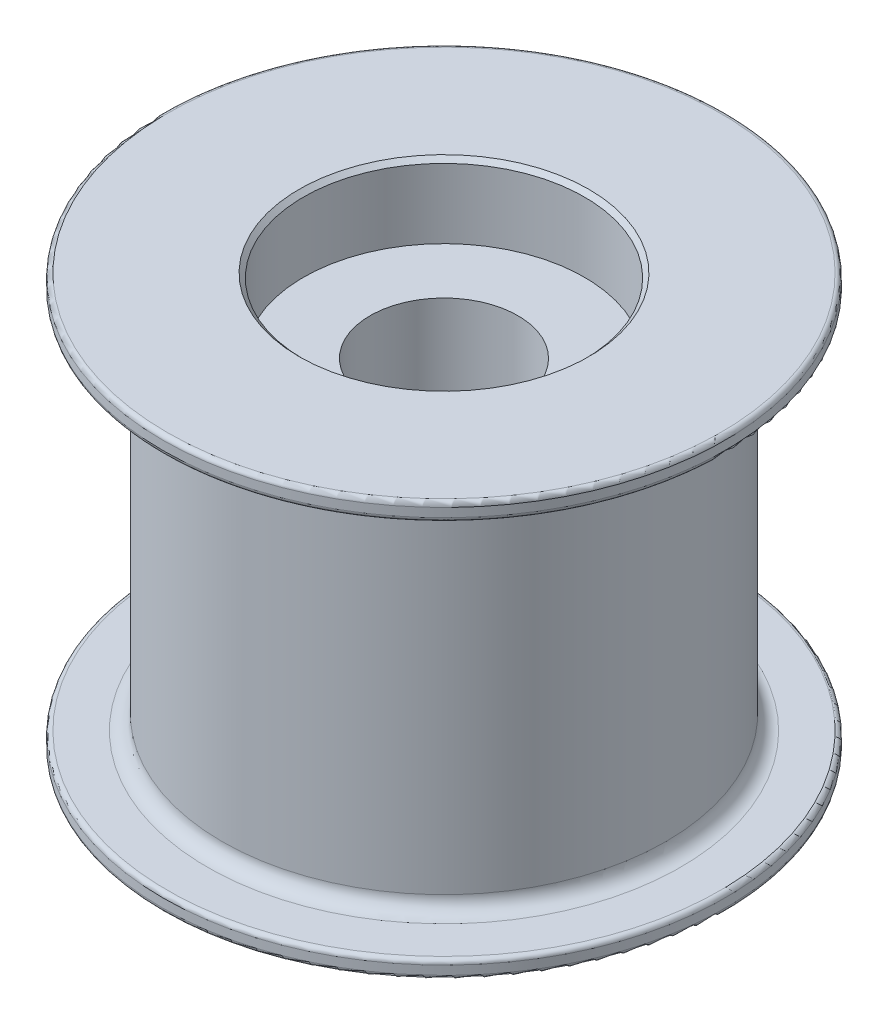
SolidWorks part; units mm, degrees
ref_plane "Front Plane" through (0, 0, 0) normal (0, 0, 1) x (1, 0, 0)
ref_plane "Top Plane" through (0, 0, 0) normal (0, 1, 0) x (1, 0, 0)
ref_plane "Right Plane" through (0, 0, 0) normal (1, 0, 0) x (0, 0, -1)
sketch "Sketch1" plane through (0, 0, 0) normal (0, 0, 1) x (1, 0, 0)
  line L0 (0, 11.9429) -> (0, 0) construction
  line L1 (-9.5, 14) -> (-19, 14)
  line L2 (-19, 14) -> (-19, 12.8)
  line L3 (-19, 12.8) -> (-15, 12.8)
  line L4 (-15, 12.8) -> (-15, 0)
  line L5 (-15, 0) -> (-5, 0)
  line L6 (-5, 0) -> (-5, 9)
  line L7 (-5, 9) -> (-9.5, 9)
  line L8 (-9.5, 9) -> (-9.5, 14)
  dimension "D1" = 1.2
  dimension "D2" = 14
  dimension "D3" = 5
  dimension "D4" = 5
  dimension "D5" = 9.5
  dimension "D6" = 4
  dimension "D7" = 19
revolve "Revolve1" add sketch "Sketch1" angle 360 about L0
fillet "Fillet1" radius 1 1 edges at (0, 12.8, 15)
chamfer "Chamfer1" distance 0.3 angle 45 1 edges at (0, 14, 9.5)
fillet "Fillet2" radius 0.3 2 edges at (0, 14, 19) (0, 12.8, 19)
mirror "Mirror1" about plane through (-15, 0, 0) normal (0, -1, 0) of bodies 101
ref_axis "Axis1" through (0, -11.8, 0) along (0, 1, 0)
